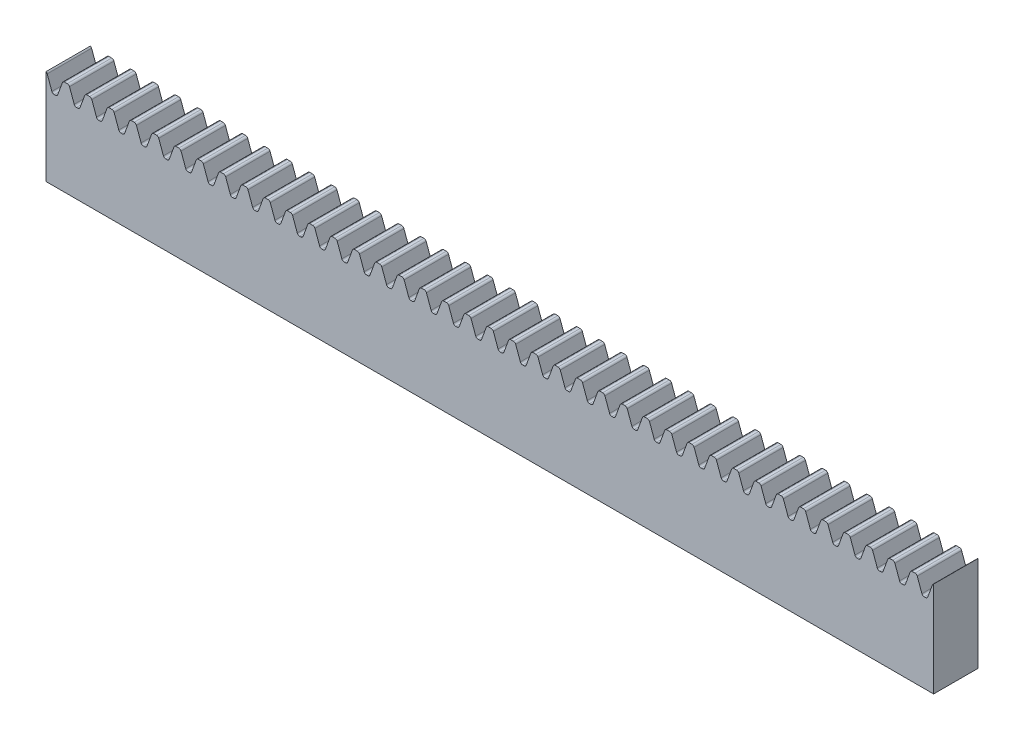
SolidWorks part; units mm, degrees
ref_plane "Front Plane" through (0, 0, 0) normal (0, 0, 1) x (1, 0, 0)
ref_plane "Top Plane" through (0, 0, 0) normal (0, 1, 0) x (1, 0, 0)
ref_plane "Right Plane" through (0, 0, 0) normal (1, 0, 0) x (0, 0, -1)
sketch "Sketch1" plane through (0, 0, 0) normal (0, 0, 1) x (1, 0, 0)
  line L0 (-50, 6.15) -> (-50, -6.15) construction
  line L1 (-50, -6.15) -> (50, -6.15) construction
  line L2 (50, -6.15) -> (50, 6.15) construction
  line L4 (0, 6.15) -> (0, -6.15) construction
  line L5 (-50, 5.35) -> (50, 5.35) construction
  line L6 (-48.0894, 6.15) -> (-47.4151, 6.15) construction
  line L7 (-47.4151, 6.15) -> (-46.7599, 4.35) construction
  line L8 (-48.0894, 6.15) -> (-48.7445, 4.35) construction
  line L9 (-48.7445, 4.35) -> (-46.7599, 4.35) construction
  line L10 (-47.7522, 6.15) -> (-47.7522, 4.35) construction
  line L11 (-50, 0) -> (-42.7257, 0) construction
  line L12 (50, 0) -> (42.7257, 0) construction
  point P15 (-45.2389, 6.15)
  point P16 (-19.5, -6.15)
  point P17 (-47.1239, 5.35)
  point P18 (-48.3805, 5.35)
  point P21 (-0.4, -6.15)
  dimension "Length" = 100
  dimension "Height" = 12.3
  dimension "Approximate Number of Teeth" = 39
  dimension "Pressure Angle" = 20
  dimension "Circular Pitch" = 2.5133
  dimension "Addendum" = 0.8
  dimension "Dedendum" = 1
  dimension "Circular Tooth Thickness" = 1.2566
  dimension "Module" = 0.8
  dimension "Rack Length" = 95.5044
  dimension "D1" = 5.0265
sketch "Sketch2" plane through (0, 0, 0) normal (1, 0, 0) x (0, 0, -1)
  line L0 (-4, 0) -> (4, 0) construction
  dimension "Face Width" = 8
sketch "Sketch3" plane through (0, 0, 0) normal (0, 0, 1) x (1, 0, 0)
  line L1 (-50, 6.15) -> (50, 6.15)
  line L2 (-50, 6.15) -> (-50, -6.15)
  line L3 (-50, -6.15) -> (50, -6.15)
  line L4 (50, 6.15) -> (50, -6.15)
extrude "Boss-Extrude1" add sketch "Sketch3" against normal up to vertex (4 mm away) and the other way up to vertex (4 mm away) up to point (0, 0, -4) other way up to point (0, 0, 4)
sketch "Sketch4" plane through (0, 0, 0) normal (0, 0, 1) x (1, 0, 0)
  line L0 (-47.7522, 6.15) -> (-45.2389, 6.15) construction
  line L9 (-46.4956, 6.15) -> (-46.4956, 4.35)
  line L10 (-46.4956, 4.35) -> (-46.7599, 4.35)
  line L11 (-46.7599, 4.35) -> (-47.4151, 6.15)
  line L12 (-47.4151, 6.15) -> (-46.4956, 6.15)
  line L13 (-48.0894, 6.15) -> (-48.7445, 4.35)
  line L14 (-48.7445, 4.35) -> (-49.0088, 4.35)
  line L15 (-49.0088, 4.35) -> (-49.0088, 6.15)
  line L16 (-49.0088, 6.15) -> (-48.0894, 6.15)
  line L17 (50, 6.15) -> (-50, 6.15) construction
  line L18 (-48.0894, 6.15) -> (-47.9014, 6.15)
  line L19 (-47.603, 6.15) -> (-47.4151, 6.15)
  arc A0 (-48.9324, 4.35) -> (-48.6802, 4.5266) centre (-48.9324, 4.6184) ccw
  arc A1 (-46.8242, 4.5266) -> (-46.572, 4.35) centre (-46.572, 4.6184) ccw
  arc A2 (-48.1536, 5.9734) -> (-47.9014, 6.15) centre (-47.9014, 5.8816) cw
  arc A3 (-47.603, 6.15) -> (-47.3508, 5.9734) centre (-47.603, 5.8816) cw
  dimension "D1" = 0.2684
extrude "Cut-Extrude1" cut sketch "Sketch4" against normal through all both and the other way through all contours L14 A0 L13 L16 L15 | L13 A2 L18 | L19 A3 L11 | L11 A1 L10 L9 L12 region at (-46.8223, 5.4223, 0) region at (-47.4415, 6.1123, 0) region at (-48.0629, 6.1123, 0) region at (-48.6821, 5.4223, 0)
pattern_linear "LPattern1" count 40 spacing 2.5133 along (1, 0, 0) count 2 spacing 2.5133 along (-1, 0, 0) of "Cut-Extrude1"
sketch "Drawing Refernce 1" plane through (0, 0, 4) normal (0, 0, 1) x (1, 0, 0)
  line L0 (-50, 0) -> (50, 0) construction
  point P6 (-35, 0)
  point P7 (-27.5, 0)
  point P8 (35, 0)
  dimension "D1" = 15
  dimension "D2" = 22.5
  dimension "D3" = 15
sketch "Sketch5" plane through (0, -6.15, 0) normal (0, -1, 0) x (1, 0, 0)
  line L1 (-50, 4) -> (50, 4)
  line L2 (-50, 4) -> (-50, -4)
  line L3 (-50, -4) -> (50, -4)
  line L4 (50, 4) -> (50, -4)
extrude "Cut-Extrude2" cut sketch "Sketch5" against normal blind 1.55
sketch "Sketch6" plane through (0, 0, -4) normal (0, 0, -1) x (-1, 0, 0)
  line L162 (-50, -4.6) -> (50, -4.6)
  line L163 (50, -4.6) -> (50, 6.1235)
  line L164 (49.8641, 5.9734) -> (49.3375, 4.5266)
  line L165 (49.0853, 4.35) -> (48.9324, 4.35)
  line L166 (48.6802, 4.5266) -> (48.1536, 5.9734)
  line L167 (47.9014, 6.15) -> (47.603, 6.15)
  line L168 (47.3508, 5.9734) -> (46.8242, 4.5266)
  line L169 (46.572, 4.35) -> (46.4192, 4.35)
  line L170 (46.1669, 4.5266) -> (45.6404, 5.9734)
  line L171 (45.3881, 6.15) -> (45.0897, 6.15)
  line L172 (44.8375, 5.9734) -> (44.3109, 4.5266)
  line L173 (44.0587, 4.35) -> (43.9059, 4.35)
  line L174 (43.6537, 4.5266) -> (43.1271, 5.9734)
  line L175 (42.8749, 6.15) -> (42.5765, 6.15)
  line L176 (42.3242, 5.9734) -> (41.7977, 4.5266)
  line L177 (41.5454, 4.35) -> (41.3926, 4.35)
  line L178 (41.1404, 4.5266) -> (40.6138, 5.9734)
  line L179 (40.3616, 6.15) -> (40.0632, 6.15)
  line L180 (39.811, 5.9734) -> (39.2844, 4.5266)
  line L181 (39.0322, 4.35) -> (38.8793, 4.35)
  line L182 (38.6271, 4.5266) -> (38.1005, 5.9734)
  line L183 (37.8483, 6.15) -> (37.5499, 6.15)
  line L184 (37.2977, 5.9734) -> (36.7711, 4.5266)
  line L185 (36.5189, 4.35) -> (36.3661, 4.35)
  line L186 (36.1138, 4.5266) -> (35.5873, 5.9734)
  line L187 (35.335, 6.15) -> (35.0366, 6.15)
  line L188 (34.7844, 5.9734) -> (34.2578, 4.5266)
  line L189 (34.0056, 4.35) -> (33.8528, 4.35)
  line L190 (33.6006, 4.5266) -> (33.074, 5.9734)
  line L191 (32.8218, 6.15) -> (32.5234, 6.15)
  line L192 (32.2711, 5.9734) -> (31.7446, 4.5266)
  line L193 (31.4923, 4.35) -> (31.3395, 4.35)
  line L194 (31.0873, 4.5266) -> (30.5607, 5.9734)
  line L195 (30.3085, 6.15) -> (30.0101, 6.15)
  line L196 (29.7579, 5.9734) -> (29.2313, 4.5266)
  line L197 (28.9791, 4.35) -> (28.8262, 4.35)
  line L198 (28.574, 4.5266) -> (28.0474, 5.9734)
  line L199 (27.7952, 6.15) -> (27.4968, 6.15)
  line L200 (27.2446, 5.9734) -> (26.718, 4.5266)
  line L201 (26.4658, 4.35) -> (26.313, 4.35)
  line L202 (26.0608, 4.5266) -> (25.5342, 5.9734)
  line L203 (25.2819, 6.15) -> (24.9835, 6.15)
  line L204 (24.7313, 5.9734) -> (24.2047, 4.5266)
  line L205 (23.9525, 4.35) -> (23.7997, 4.35)
  line L206 (23.5475, 4.5266) -> (23.0209, 5.9734)
  line L207 (22.7687, 6.15) -> (22.4703, 6.15)
  line L208 (22.218, 5.9734) -> (21.6915, 4.5266)
  line L209 (21.4392, 4.35) -> (21.2864, 4.35)
  line L210 (21.0342, 4.5266) -> (20.5076, 5.9734)
  line L211 (20.2554, 6.15) -> (19.957, 6.15)
  line L212 (19.7048, 5.9734) -> (19.1782, 4.5266)
  line L213 (18.926, 4.35) -> (18.7731, 4.35)
  line L214 (18.5209, 4.5266) -> (17.9943, 5.9734)
  line L215 (17.7421, 6.15) -> (17.4437, 6.15)
  line L216 (17.1915, 5.9734) -> (16.6649, 4.5266)
  line L217 (16.4127, 4.35) -> (16.2599, 4.35)
  line L218 (16.0077, 4.5266) -> (15.4811, 5.9734)
  line L219 (15.2288, 6.15) -> (14.9304, 6.15)
  line L220 (14.6782, 5.9734) -> (14.1516, 4.5266)
  line L221 (13.8994, 4.35) -> (13.7466, 4.35)
  line L222 (13.4944, 4.5266) -> (12.9678, 5.9734)
  line L223 (12.7156, 6.15) -> (12.4172, 6.15)
  line L224 (12.1649, 5.9734) -> (11.6384, 4.5266)
  line L225 (11.3861, 4.35) -> (11.2333, 4.35)
  line L226 (10.9811, 4.5266) -> (10.4545, 5.9734)
  line L227 (10.2023, 6.15) -> (9.9039, 6.15)
  line L228 (9.6517, 5.9734) -> (9.1251, 4.5266)
  line L229 (8.8729, 4.35) -> (8.72, 4.35)
  line L230 (8.4678, 4.5266) -> (7.9412, 5.9734)
  line L231 (7.689, 6.15) -> (7.3906, 6.15)
  line L232 (7.1384, 5.9734) -> (6.6118, 4.5266)
  line L233 (6.3596, 4.35) -> (6.2068, 4.35)
  line L234 (5.9546, 4.5266) -> (5.428, 5.9734)
  line L235 (5.1758, 6.15) -> (4.8773, 6.15)
  line L236 (4.6251, 5.9734) -> (4.0985, 4.5266)
  line L237 (3.8463, 4.35) -> (3.6935, 4.35)
  line L238 (3.4413, 4.5266) -> (2.9147, 5.9734)
  line L239 (2.6625, 6.15) -> (2.3641, 6.15)
  line L240 (2.1119, 5.9734) -> (1.5853, 4.5266)
  line L241 (1.333, 4.35) -> (1.1802, 4.35)
  line L242 (0.928, 4.5266) -> (0.4014, 5.9734)
  line L243 (0.1492, 6.15) -> (-0.1492, 6.15)
  line L244 (-0.4014, 5.9734) -> (-0.928, 4.5266)
  line L245 (-1.1802, 4.35) -> (-1.333, 4.35)
  line L246 (-1.5853, 4.5266) -> (-2.1119, 5.9734)
  line L247 (-2.3641, 6.15) -> (-2.6625, 6.15)
  line L248 (-2.9147, 5.9734) -> (-3.4413, 4.5266)
  line L249 (-3.6935, 4.35) -> (-3.8463, 4.35)
  line L250 (-4.0985, 4.5266) -> (-4.6251, 5.9734)
  line L251 (-4.8773, 6.15) -> (-5.1758, 6.15)
  line L252 (-5.428, 5.9734) -> (-5.9546, 4.5266)
  line L253 (-6.2068, 4.35) -> (-6.3596, 4.35)
  line L254 (-6.6118, 4.5266) -> (-7.1384, 5.9734)
  line L255 (-7.3906, 6.15) -> (-7.689, 6.15)
  line L256 (-7.9412, 5.9734) -> (-8.4678, 4.5266)
  line L257 (-8.72, 4.35) -> (-8.8729, 4.35)
  line L258 (-9.1251, 4.5266) -> (-9.6517, 5.9734)
  line L259 (-9.9039, 6.15) -> (-10.2023, 6.15)
  line L260 (-10.4545, 5.9734) -> (-10.9811, 4.5266)
  line L261 (-11.2333, 4.35) -> (-11.3861, 4.35)
  line L262 (-11.6384, 4.5266) -> (-12.1649, 5.9734)
  line L263 (-12.4172, 6.15) -> (-12.7156, 6.15)
  line L264 (-12.9678, 5.9734) -> (-13.4944, 4.5266)
  line L265 (-13.7466, 4.35) -> (-13.8994, 4.35)
  line L266 (-14.1516, 4.5266) -> (-14.6782, 5.9734)
  line L267 (-14.9304, 6.15) -> (-15.2288, 6.15)
  line L268 (-15.4811, 5.9734) -> (-16.0077, 4.5266)
  line L269 (-16.2599, 4.35) -> (-16.4127, 4.35)
  line L270 (-16.6649, 4.5266) -> (-17.1915, 5.9734)
  line L271 (-17.4437, 6.15) -> (-17.7421, 6.15)
  line L272 (-17.9943, 5.9734) -> (-18.5209, 4.5266)
  line L273 (-18.7731, 4.35) -> (-18.926, 4.35)
  line L274 (-19.1782, 4.5266) -> (-19.7048, 5.9734)
  line L275 (-19.957, 6.15) -> (-20.2554, 6.15)
  line L276 (-20.5076, 5.9734) -> (-21.0342, 4.5266)
  line L277 (-21.2864, 4.35) -> (-21.4392, 4.35)
  line L278 (-21.6915, 4.5266) -> (-22.218, 5.9734)
  line L279 (-22.4703, 6.15) -> (-22.7687, 6.15)
  line L280 (-23.0209, 5.9734) -> (-23.5475, 4.5266)
  line L281 (-23.7997, 4.35) -> (-23.9525, 4.35)
  line L282 (-24.2047, 4.5266) -> (-24.7313, 5.9734)
  line L283 (-24.9835, 6.15) -> (-25.2819, 6.15)
  line L284 (-25.5342, 5.9734) -> (-26.0608, 4.5266)
  line L285 (-26.313, 4.35) -> (-26.4658, 4.35)
  line L286 (-26.718, 4.5266) -> (-27.2446, 5.9734)
  line L287 (-27.4968, 6.15) -> (-27.7952, 6.15)
  line L288 (-28.0474, 5.9734) -> (-28.574, 4.5266)
  line L289 (-28.8262, 4.35) -> (-28.9791, 4.35)
  line L290 (-29.2313, 4.5266) -> (-29.7579, 5.9734)
  line L291 (-30.0101, 6.15) -> (-30.3085, 6.15)
  line L292 (-30.5607, 5.9734) -> (-31.0873, 4.5266)
  line L293 (-31.3395, 4.35) -> (-31.4923, 4.35)
  line L294 (-31.7446, 4.5266) -> (-32.2711, 5.9734)
  line L295 (-32.5234, 6.15) -> (-32.8218, 6.15)
  line L296 (-33.074, 5.9734) -> (-33.6006, 4.5266)
  line L297 (-33.8528, 4.35) -> (-34.0056, 4.35)
  line L298 (-34.2578, 4.5266) -> (-34.7844, 5.9734)
  line L299 (-35.0366, 6.15) -> (-35.335, 6.15)
  line L300 (-35.5873, 5.9734) -> (-36.1138, 4.5266)
  line L301 (-36.3661, 4.35) -> (-36.5189, 4.35)
  line L302 (-36.7711, 4.5266) -> (-37.2977, 5.9734)
  line L303 (-37.5499, 6.15) -> (-37.8483, 6.15)
  line L304 (-38.1005, 5.9734) -> (-38.6271, 4.5266)
  line L305 (-38.8793, 4.35) -> (-39.0322, 4.35)
  line L306 (-39.2844, 4.5266) -> (-39.811, 5.9734)
  line L307 (-40.0632, 6.15) -> (-40.3616, 6.15)
  line L308 (-40.6138, 5.9734) -> (-41.1404, 4.5266)
  line L309 (-41.3926, 4.35) -> (-41.5454, 4.35)
  line L310 (-41.7977, 4.5266) -> (-42.3242, 5.9734)
  line L311 (-42.5765, 6.15) -> (-42.8749, 6.15)
  line L312 (-43.1271, 5.9734) -> (-43.6537, 4.5266)
  line L313 (-43.9059, 4.35) -> (-44.0587, 4.35)
  line L314 (-44.3109, 4.5266) -> (-44.8375, 5.9734)
  line L315 (-45.0897, 6.15) -> (-45.3881, 6.15)
  line L316 (-45.6404, 5.9734) -> (-46.1669, 4.5266)
  line L317 (-46.4192, 4.35) -> (-46.572, 4.35)
  line L318 (-46.8242, 4.5266) -> (-47.3508, 5.9734)
  line L319 (-47.603, 6.15) -> (-47.9014, 6.15)
  line L320 (-48.1536, 5.9734) -> (-48.6802, 4.5266)
  line L321 (-48.9324, 4.35) -> (-49.0853, 4.35)
  line L322 (-49.3375, 4.5266) -> (-49.8641, 5.9734)
  line L323 (-50, 6.1235) -> (-50, -4.6)
  line L325 (50, -4.6) -> (50, 6.1235)
  line L326 (49.8641, 5.9734) -> (49.3375, 4.5266)
  line L327 (49.0853, 4.35) -> (48.9324, 4.35)
  line L328 (48.6802, 4.5266) -> (48.1536, 5.9734)
  line L329 (47.9014, 6.15) -> (47.603, 6.15)
  line L330 (47.3508, 5.9734) -> (46.8242, 4.5266)
  line L331 (46.572, 4.35) -> (46.4192, 4.35)
  line L332 (46.1669, 4.5266) -> (45.6404, 5.9734)
  line L333 (45.3881, 6.15) -> (45.0897, 6.15)
  line L334 (44.8375, 5.9734) -> (44.3109, 4.5266)
  line L335 (44.0587, 4.35) -> (43.9059, 4.35)
  line L336 (43.6537, 4.5266) -> (43.1271, 5.9734)
  line L337 (42.8749, 6.15) -> (42.5765, 6.15)
  line L338 (42.3242, 5.9734) -> (41.7977, 4.5266)
  line L339 (41.5454, 4.35) -> (41.3926, 4.35)
  line L340 (41.1404, 4.5266) -> (40.6138, 5.9734)
  line L341 (40.3616, 6.15) -> (40.0632, 6.15)
  line L342 (39.811, 5.9734) -> (39.2844, 4.5266)
  line L343 (39.0322, 4.35) -> (38.8793, 4.35)
  line L344 (38.6271, 4.5266) -> (38.1005, 5.9734)
  line L345 (37.8483, 6.15) -> (37.5499, 6.15)
  line L346 (37.2977, 5.9734) -> (36.7711, 4.5266)
  line L347 (36.5189, 4.35) -> (36.3661, 4.35)
  line L348 (36.1138, 4.5266) -> (35.5873, 5.9734)
  line L349 (35.335, 6.15) -> (35.0366, 6.15)
  line L350 (34.7844, 5.9734) -> (34.2578, 4.5266)
  line L351 (34.0056, 4.35) -> (33.8528, 4.35)
  line L352 (33.6006, 4.5266) -> (33.074, 5.9734)
  line L353 (32.8218, 6.15) -> (32.5234, 6.15)
  line L354 (32.2711, 5.9734) -> (31.7446, 4.5266)
  line L355 (31.4923, 4.35) -> (31.3395, 4.35)
  line L356 (31.0873, 4.5266) -> (30.5607, 5.9734)
  line L357 (30.3085, 6.15) -> (30.0101, 6.15)
  line L358 (29.7579, 5.9734) -> (29.2313, 4.5266)
  line L359 (28.9791, 4.35) -> (28.8262, 4.35)
  line L360 (28.574, 4.5266) -> (28.0474, 5.9734)
  line L361 (27.7952, 6.15) -> (27.4968, 6.15)
  line L362 (27.2446, 5.9734) -> (26.718, 4.5266)
  line L363 (26.4658, 4.35) -> (26.313, 4.35)
  line L364 (26.0608, 4.5266) -> (25.5342, 5.9734)
  line L365 (25.2819, 6.15) -> (24.9835, 6.15)
  line L366 (24.7313, 5.9734) -> (24.2047, 4.5266)
  line L367 (23.9525, 4.35) -> (23.7997, 4.35)
  line L368 (23.5475, 4.5266) -> (23.0209, 5.9734)
  line L369 (22.7687, 6.15) -> (22.4703, 6.15)
  line L370 (22.218, 5.9734) -> (21.6915, 4.5266)
  line L371 (21.4392, 4.35) -> (21.2864, 4.35)
  line L372 (21.0342, 4.5266) -> (20.5076, 5.9734)
  line L373 (20.2554, 6.15) -> (19.957, 6.15)
  line L374 (19.7048, 5.9734) -> (19.1782, 4.5266)
  line L375 (18.926, 4.35) -> (18.7731, 4.35)
  line L376 (18.5209, 4.5266) -> (17.9943, 5.9734)
  line L377 (17.7421, 6.15) -> (17.4437, 6.15)
  line L378 (17.1915, 5.9734) -> (16.6649, 4.5266)
  line L379 (16.4127, 4.35) -> (16.2599, 4.35)
  line L380 (16.0077, 4.5266) -> (15.4811, 5.9734)
  line L381 (15.2288, 6.15) -> (14.9304, 6.15)
  line L382 (14.6782, 5.9734) -> (14.1516, 4.5266)
  line L383 (13.8994, 4.35) -> (13.7466, 4.35)
  line L384 (13.4944, 4.5266) -> (12.9678, 5.9734)
  line L385 (12.7156, 6.15) -> (12.4172, 6.15)
  line L386 (12.1649, 5.9734) -> (11.6384, 4.5266)
  line L387 (11.3861, 4.35) -> (11.2333, 4.35)
  line L388 (10.9811, 4.5266) -> (10.4545, 5.9734)
  line L389 (10.2023, 6.15) -> (9.9039, 6.15)
  line L390 (9.6517, 5.9734) -> (9.1251, 4.5266)
  line L391 (8.8729, 4.35) -> (8.72, 4.35)
  line L392 (8.4678, 4.5266) -> (7.9412, 5.9734)
  line L393 (7.689, 6.15) -> (7.3906, 6.15)
  line L394 (7.1384, 5.9734) -> (6.6118, 4.5266)
  line L395 (6.3596, 4.35) -> (6.2068, 4.35)
  line L396 (5.9546, 4.5266) -> (5.428, 5.9734)
  line L397 (5.1758, 6.15) -> (4.8773, 6.15)
  line L398 (4.6251, 5.9734) -> (4.0985, 4.5266)
  line L399 (3.8463, 4.35) -> (3.6935, 4.35)
  line L400 (3.4413, 4.5266) -> (2.9147, 5.9734)
  line L401 (2.6625, 6.15) -> (2.3641, 6.15)
  line L402 (2.1119, 5.9734) -> (1.5853, 4.5266)
  line L403 (1.333, 4.35) -> (1.1802, 4.35)
  line L404 (0.928, 4.5266) -> (0.4014, 5.9734)
  line L405 (0.1492, 6.15) -> (-0.1492, 6.15)
  line L406 (-0.4014, 5.9734) -> (-0.928, 4.5266)
  line L407 (-1.1802, 4.35) -> (-1.333, 4.35)
  line L408 (-1.5853, 4.5266) -> (-2.1119, 5.9734)
  line L409 (-2.3641, 6.15) -> (-2.6625, 6.15)
  line L410 (-2.9147, 5.9734) -> (-3.4413, 4.5266)
  line L411 (-3.6935, 4.35) -> (-3.8463, 4.35)
  line L412 (-4.0985, 4.5266) -> (-4.6251, 5.9734)
  line L413 (-4.8773, 6.15) -> (-5.1758, 6.15)
  line L414 (-5.428, 5.9734) -> (-5.9546, 4.5266)
  line L415 (-6.2068, 4.35) -> (-6.3596, 4.35)
  line L416 (-6.6118, 4.5266) -> (-7.1384, 5.9734)
  line L417 (-7.3906, 6.15) -> (-7.689, 6.15)
  line L418 (-7.9412, 5.9734) -> (-8.4678, 4.5266)
  line L419 (-8.72, 4.35) -> (-8.8729, 4.35)
  line L420 (-9.1251, 4.5266) -> (-9.6517, 5.9734)
  line L421 (-9.9039, 6.15) -> (-10.2023, 6.15)
  line L422 (-10.4545, 5.9734) -> (-10.9811, 4.5266)
  line L423 (-11.2333, 4.35) -> (-11.3861, 4.35)
  line L424 (-11.6384, 4.5266) -> (-12.1649, 5.9734)
  line L425 (-12.4172, 6.15) -> (-12.7156, 6.15)
  line L426 (-12.9678, 5.9734) -> (-13.4944, 4.5266)
  line L427 (-13.7466, 4.35) -> (-13.8994, 4.35)
  line L428 (-14.1516, 4.5266) -> (-14.6782, 5.9734)
  line L429 (-14.9304, 6.15) -> (-15.2288, 6.15)
  line L430 (-15.4811, 5.9734) -> (-16.0077, 4.5266)
  line L431 (-16.2599, 4.35) -> (-16.4127, 4.35)
  line L432 (-16.6649, 4.5266) -> (-17.1915, 5.9734)
  line L433 (-17.4437, 6.15) -> (-17.7421, 6.15)
  line L434 (-17.9943, 5.9734) -> (-18.5209, 4.5266)
  line L435 (-18.7731, 4.35) -> (-18.926, 4.35)
  line L436 (-19.1782, 4.5266) -> (-19.7048, 5.9734)
  line L437 (-19.957, 6.15) -> (-20.2554, 6.15)
  line L438 (-20.5076, 5.9734) -> (-21.0342, 4.5266)
  line L439 (-21.2864, 4.35) -> (-21.4392, 4.35)
  line L440 (-21.6915, 4.5266) -> (-22.218, 5.9734)
  line L441 (-22.4703, 6.15) -> (-22.7687, 6.15)
  line L442 (-23.0209, 5.9734) -> (-23.5475, 4.5266)
  line L443 (-23.7997, 4.35) -> (-23.9525, 4.35)
  line L444 (-24.2047, 4.5266) -> (-24.7313, 5.9734)
  line L445 (-24.9835, 6.15) -> (-25.2819, 6.15)
  line L446 (-25.5342, 5.9734) -> (-26.0608, 4.5266)
  line L447 (-26.313, 4.35) -> (-26.4658, 4.35)
  line L448 (-26.718, 4.5266) -> (-27.2446, 5.9734)
  line L449 (-27.4968, 6.15) -> (-27.7952, 6.15)
  line L450 (-28.0474, 5.9734) -> (-28.574, 4.5266)
  line L451 (-28.8262, 4.35) -> (-28.9791, 4.35)
  line L452 (-29.2313, 4.5266) -> (-29.7579, 5.9734)
  line L453 (-30.0101, 6.15) -> (-30.3085, 6.15)
  line L454 (-30.5607, 5.9734) -> (-31.0873, 4.5266)
  line L455 (-31.3395, 4.35) -> (-31.4923, 4.35)
  line L456 (-31.7446, 4.5266) -> (-32.2711, 5.9734)
  line L457 (-32.5234, 6.15) -> (-32.8218, 6.15)
  line L458 (-33.074, 5.9734) -> (-33.6006, 4.5266)
  line L459 (-33.8528, 4.35) -> (-34.0056, 4.35)
  line L460 (-34.2578, 4.5266) -> (-34.7844, 5.9734)
  line L461 (-35.0366, 6.15) -> (-35.335, 6.15)
  line L462 (-35.5873, 5.9734) -> (-36.1138, 4.5266)
  line L463 (-36.3661, 4.35) -> (-36.5189, 4.35)
  line L464 (-36.7711, 4.5266) -> (-37.2977, 5.9734)
  line L465 (-37.5499, 6.15) -> (-37.8483, 6.15)
  line L466 (-38.1005, 5.9734) -> (-38.6271, 4.5266)
  line L467 (-38.8793, 4.35) -> (-39.0322, 4.35)
  line L468 (-39.2844, 4.5266) -> (-39.811, 5.9734)
  line L469 (-40.0632, 6.15) -> (-40.3616, 6.15)
  line L470 (-40.6138, 5.9734) -> (-41.1404, 4.5266)
  line L471 (-41.3926, 4.35) -> (-41.5454, 4.35)
  line L472 (-41.7977, 4.5266) -> (-42.3242, 5.9734)
  line L473 (-42.5765, 6.15) -> (-42.8749, 6.15)
  line L474 (-43.1271, 5.9734) -> (-43.6537, 4.5266)
  line L475 (-43.9059, 4.35) -> (-44.0587, 4.35)
  line L476 (-44.3109, 4.5266) -> (-44.8375, 5.9734)
  line L477 (-45.0897, 6.15) -> (-45.3881, 6.15)
  line L478 (-45.6404, 5.9734) -> (-46.1669, 4.5266)
  line L479 (-46.4192, 4.35) -> (-46.572, 4.35)
  line L480 (-46.8242, 4.5266) -> (-47.3508, 5.9734)
  line L481 (-47.603, 6.15) -> (-47.9014, 6.15)
  line L482 (-48.1536, 5.9734) -> (-48.6802, 4.5266)
  line L483 (-48.9324, 4.35) -> (-49.0853, 4.35)
  line L484 (-49.3375, 4.5266) -> (-49.8641, 5.9734)
  line L485 (-50, 6.1235) -> (-50, -4.6)
  line L487 (-50, -4.6) -> (50, -4.6)
  arc A160 (50, 6.1235) -> (49.8641, 5.9734) centre (50.1163, 5.8816) ccw
  arc A161 (49.0853, 4.35) -> (49.3375, 4.5266) centre (49.0853, 4.6184) ccw
  arc A162 (48.6802, 4.5266) -> (48.9324, 4.35) centre (48.9324, 4.6184) ccw
  arc A163 (48.1536, 5.9734) -> (47.9014, 6.15) centre (47.9014, 5.8816) ccw
  arc A164 (47.603, 6.15) -> (47.3508, 5.9734) centre (47.603, 5.8816) ccw
  arc A165 (46.572, 4.35) -> (46.8242, 4.5266) centre (46.572, 4.6184) ccw
  arc A166 (46.1669, 4.5266) -> (46.4192, 4.35) centre (46.4192, 4.6184) ccw
  arc A167 (45.6404, 5.9734) -> (45.3881, 6.15) centre (45.3881, 5.8816) ccw
  arc A168 (45.0897, 6.15) -> (44.8375, 5.9734) centre (45.0897, 5.8816) ccw
  arc A169 (44.0587, 4.35) -> (44.3109, 4.5266) centre (44.0587, 4.6184) ccw
  arc A170 (43.6537, 4.5266) -> (43.9059, 4.35) centre (43.9059, 4.6184) ccw
  arc A171 (43.1271, 5.9734) -> (42.8749, 6.15) centre (42.8749, 5.8816) ccw
  arc A172 (42.5765, 6.15) -> (42.3242, 5.9734) centre (42.5765, 5.8816) ccw
  arc A173 (41.5454, 4.35) -> (41.7977, 4.5266) centre (41.5454, 4.6184) ccw
  arc A174 (41.1404, 4.5266) -> (41.3926, 4.35) centre (41.3926, 4.6184) ccw
  arc A175 (40.6138, 5.9734) -> (40.3616, 6.15) centre (40.3616, 5.8816) ccw
  arc A176 (40.0632, 6.15) -> (39.811, 5.9734) centre (40.0632, 5.8816) ccw
  arc A177 (39.0322, 4.35) -> (39.2844, 4.5266) centre (39.0322, 4.6184) ccw
  arc A178 (38.6271, 4.5266) -> (38.8793, 4.35) centre (38.8793, 4.6184) ccw
  arc A179 (38.1005, 5.9734) -> (37.8483, 6.15) centre (37.8483, 5.8816) ccw
  arc A180 (37.5499, 6.15) -> (37.2977, 5.9734) centre (37.5499, 5.8816) ccw
  arc A181 (36.5189, 4.35) -> (36.7711, 4.5266) centre (36.5189, 4.6184) ccw
  arc A182 (36.1138, 4.5266) -> (36.3661, 4.35) centre (36.3661, 4.6184) ccw
  arc A183 (35.5873, 5.9734) -> (35.335, 6.15) centre (35.335, 5.8816) ccw
  arc A184 (35.0366, 6.15) -> (34.7844, 5.9734) centre (35.0366, 5.8816) ccw
  arc A185 (34.0056, 4.35) -> (34.2578, 4.5266) centre (34.0056, 4.6184) ccw
  arc A186 (33.6006, 4.5266) -> (33.8528, 4.35) centre (33.8528, 4.6184) ccw
  arc A187 (33.074, 5.9734) -> (32.8218, 6.15) centre (32.8218, 5.8816) ccw
  arc A188 (32.5234, 6.15) -> (32.2711, 5.9734) centre (32.5234, 5.8816) ccw
  arc A189 (31.4923, 4.35) -> (31.7446, 4.5266) centre (31.4923, 4.6184) ccw
  arc A190 (31.0873, 4.5266) -> (31.3395, 4.35) centre (31.3395, 4.6184) ccw
  arc A191 (30.5607, 5.9734) -> (30.3085, 6.15) centre (30.3085, 5.8816) ccw
  arc A192 (30.0101, 6.15) -> (29.7579, 5.9734) centre (30.0101, 5.8816) ccw
  arc A193 (28.9791, 4.35) -> (29.2313, 4.5266) centre (28.9791, 4.6184) ccw
  arc A194 (28.574, 4.5266) -> (28.8262, 4.35) centre (28.8262, 4.6184) ccw
  arc A195 (28.0474, 5.9734) -> (27.7952, 6.15) centre (27.7952, 5.8816) ccw
  arc A196 (27.4968, 6.15) -> (27.2446, 5.9734) centre (27.4968, 5.8816) ccw
  arc A197 (26.4658, 4.35) -> (26.718, 4.5266) centre (26.4658, 4.6184) ccw
  arc A198 (26.0608, 4.5266) -> (26.313, 4.35) centre (26.313, 4.6184) ccw
  arc A199 (25.5342, 5.9734) -> (25.2819, 6.15) centre (25.2819, 5.8816) ccw
  arc A200 (24.9835, 6.15) -> (24.7313, 5.9734) centre (24.9835, 5.8816) ccw
  arc A201 (23.9525, 4.35) -> (24.2047, 4.5266) centre (23.9525, 4.6184) ccw
  arc A202 (23.5475, 4.5266) -> (23.7997, 4.35) centre (23.7997, 4.6184) ccw
  arc A203 (23.0209, 5.9734) -> (22.7687, 6.15) centre (22.7687, 5.8816) ccw
  arc A204 (22.4703, 6.15) -> (22.218, 5.9734) centre (22.4703, 5.8816) ccw
  arc A205 (21.4392, 4.35) -> (21.6915, 4.5266) centre (21.4392, 4.6184) ccw
  arc A206 (21.0342, 4.5266) -> (21.2864, 4.35) centre (21.2864, 4.6184) ccw
  arc A207 (20.5076, 5.9734) -> (20.2554, 6.15) centre (20.2554, 5.8816) ccw
  arc A208 (19.957, 6.15) -> (19.7048, 5.9734) centre (19.957, 5.8816) ccw
  arc A209 (18.926, 4.35) -> (19.1782, 4.5266) centre (18.926, 4.6184) ccw
  arc A210 (18.5209, 4.5266) -> (18.7731, 4.35) centre (18.7731, 4.6184) ccw
  arc A211 (17.9943, 5.9734) -> (17.7421, 6.15) centre (17.7421, 5.8816) ccw
  arc A212 (17.4437, 6.15) -> (17.1915, 5.9734) centre (17.4437, 5.8816) ccw
  arc A213 (16.4127, 4.35) -> (16.6649, 4.5266) centre (16.4127, 4.6184) ccw
  arc A214 (16.0077, 4.5266) -> (16.2599, 4.35) centre (16.2599, 4.6184) ccw
  arc A215 (15.4811, 5.9734) -> (15.2288, 6.15) centre (15.2288, 5.8816) ccw
  arc A216 (14.9304, 6.15) -> (14.6782, 5.9734) centre (14.9304, 5.8816) ccw
  arc A217 (13.8994, 4.35) -> (14.1516, 4.5266) centre (13.8994, 4.6184) ccw
  arc A218 (13.4944, 4.5266) -> (13.7466, 4.35) centre (13.7466, 4.6184) ccw
  arc A219 (12.9678, 5.9734) -> (12.7156, 6.15) centre (12.7156, 5.8816) ccw
  arc A220 (12.4172, 6.15) -> (12.1649, 5.9734) centre (12.4172, 5.8816) ccw
  arc A221 (11.3861, 4.35) -> (11.6384, 4.5266) centre (11.3861, 4.6184) ccw
  arc A222 (10.9811, 4.5266) -> (11.2333, 4.35) centre (11.2333, 4.6184) ccw
  arc A223 (10.4545, 5.9734) -> (10.2023, 6.15) centre (10.2023, 5.8816) ccw
  arc A224 (9.9039, 6.15) -> (9.6517, 5.9734) centre (9.9039, 5.8816) ccw
  arc A225 (8.8729, 4.35) -> (9.1251, 4.5266) centre (8.8729, 4.6184) ccw
  arc A226 (8.4678, 4.5266) -> (8.72, 4.35) centre (8.72, 4.6184) ccw
  arc A227 (7.9412, 5.9734) -> (7.689, 6.15) centre (7.689, 5.8816) ccw
  arc A228 (7.3906, 6.15) -> (7.1384, 5.9734) centre (7.3906, 5.8816) ccw
  arc A229 (6.3596, 4.35) -> (6.6118, 4.5266) centre (6.3596, 4.6184) ccw
  arc A230 (5.9546, 4.5266) -> (6.2068, 4.35) centre (6.2068, 4.6184) ccw
  arc A231 (5.428, 5.9734) -> (5.1758, 6.15) centre (5.1758, 5.8816) ccw
  arc A232 (4.8773, 6.15) -> (4.6251, 5.9734) centre (4.8773, 5.8816) ccw
  arc A233 (3.8463, 4.35) -> (4.0985, 4.5266) centre (3.8463, 4.6184) ccw
  arc A234 (3.4413, 4.5266) -> (3.6935, 4.35) centre (3.6935, 4.6184) ccw
  arc A235 (2.9147, 5.9734) -> (2.6625, 6.15) centre (2.6625, 5.8816) ccw
  arc A236 (2.3641, 6.15) -> (2.1119, 5.9734) centre (2.3641, 5.8816) ccw
  arc A237 (1.333, 4.35) -> (1.5853, 4.5266) centre (1.333, 4.6184) ccw
  arc A238 (0.928, 4.5266) -> (1.1802, 4.35) centre (1.1802, 4.6184) ccw
  arc A239 (0.4014, 5.9734) -> (0.1492, 6.15) centre (0.1492, 5.8816) ccw
  arc A240 (-0.1492, 6.15) -> (-0.4014, 5.9734) centre (-0.1492, 5.8816) ccw
  arc A241 (-1.1802, 4.35) -> (-0.928, 4.5266) centre (-1.1802, 4.6184) ccw
  arc A242 (-1.5853, 4.5266) -> (-1.333, 4.35) centre (-1.333, 4.6184) ccw
  arc A243 (-2.1119, 5.9734) -> (-2.3641, 6.15) centre (-2.3641, 5.8816) ccw
  arc A244 (-2.6625, 6.15) -> (-2.9147, 5.9734) centre (-2.6625, 5.8816) ccw
  arc A245 (-3.6935, 4.35) -> (-3.4413, 4.5266) centre (-3.6935, 4.6184) ccw
  arc A246 (-4.0985, 4.5266) -> (-3.8463, 4.35) centre (-3.8463, 4.6184) ccw
  arc A247 (-4.6251, 5.9734) -> (-4.8773, 6.15) centre (-4.8773, 5.8816) ccw
  arc A248 (-5.1758, 6.15) -> (-5.428, 5.9734) centre (-5.1758, 5.8816) ccw
  arc A249 (-6.2068, 4.35) -> (-5.9546, 4.5266) centre (-6.2068, 4.6184) ccw
  arc A250 (-6.6118, 4.5266) -> (-6.3596, 4.35) centre (-6.3596, 4.6184) ccw
  arc A251 (-7.1384, 5.9734) -> (-7.3906, 6.15) centre (-7.3906, 5.8816) ccw
  arc A252 (-7.689, 6.15) -> (-7.9412, 5.9734) centre (-7.689, 5.8816) ccw
  arc A253 (-8.72, 4.35) -> (-8.4678, 4.5266) centre (-8.72, 4.6184) ccw
  arc A254 (-9.1251, 4.5266) -> (-8.8729, 4.35) centre (-8.8729, 4.6184) ccw
  arc A255 (-9.6517, 5.9734) -> (-9.9039, 6.15) centre (-9.9039, 5.8816) ccw
  arc A256 (-10.2023, 6.15) -> (-10.4545, 5.9734) centre (-10.2023, 5.8816) ccw
  arc A257 (-11.2333, 4.35) -> (-10.9811, 4.5266) centre (-11.2333, 4.6184) ccw
  arc A258 (-11.6384, 4.5266) -> (-11.3861, 4.35) centre (-11.3861, 4.6184) ccw
  arc A259 (-12.1649, 5.9734) -> (-12.4172, 6.15) centre (-12.4172, 5.8816) ccw
  arc A260 (-12.7156, 6.15) -> (-12.9678, 5.9734) centre (-12.7156, 5.8816) ccw
  arc A261 (-13.7466, 4.35) -> (-13.4944, 4.5266) centre (-13.7466, 4.6184) ccw
  arc A262 (-14.1516, 4.5266) -> (-13.8994, 4.35) centre (-13.8994, 4.6184) ccw
  arc A263 (-14.6782, 5.9734) -> (-14.9304, 6.15) centre (-14.9304, 5.8816) ccw
  arc A264 (-15.2288, 6.15) -> (-15.4811, 5.9734) centre (-15.2288, 5.8816) ccw
  arc A265 (-16.2599, 4.35) -> (-16.0077, 4.5266) centre (-16.2599, 4.6184) ccw
  arc A266 (-16.6649, 4.5266) -> (-16.4127, 4.35) centre (-16.4127, 4.6184) ccw
  arc A267 (-17.1915, 5.9734) -> (-17.4437, 6.15) centre (-17.4437, 5.8816) ccw
  arc A268 (-17.7421, 6.15) -> (-17.9943, 5.9734) centre (-17.7421, 5.8816) ccw
  arc A269 (-18.7731, 4.35) -> (-18.5209, 4.5266) centre (-18.7731, 4.6184) ccw
  arc A270 (-19.1782, 4.5266) -> (-18.926, 4.35) centre (-18.926, 4.6184) ccw
  arc A271 (-19.7048, 5.9734) -> (-19.957, 6.15) centre (-19.957, 5.8816) ccw
  arc A272 (-20.2554, 6.15) -> (-20.5076, 5.9734) centre (-20.2554, 5.8816) ccw
  arc A273 (-21.2864, 4.35) -> (-21.0342, 4.5266) centre (-21.2864, 4.6184) ccw
  arc A274 (-21.6915, 4.5266) -> (-21.4392, 4.35) centre (-21.4392, 4.6184) ccw
  arc A275 (-22.218, 5.9734) -> (-22.4703, 6.15) centre (-22.4703, 5.8816) ccw
  arc A276 (-22.7687, 6.15) -> (-23.0209, 5.9734) centre (-22.7687, 5.8816) ccw
  arc A277 (-23.7997, 4.35) -> (-23.5475, 4.5266) centre (-23.7997, 4.6184) ccw
  arc A278 (-24.2047, 4.5266) -> (-23.9525, 4.35) centre (-23.9525, 4.6184) ccw
  arc A279 (-24.7313, 5.9734) -> (-24.9835, 6.15) centre (-24.9835, 5.8816) ccw
  arc A280 (-25.2819, 6.15) -> (-25.5342, 5.9734) centre (-25.2819, 5.8816) ccw
  arc A281 (-26.313, 4.35) -> (-26.0608, 4.5266) centre (-26.313, 4.6184) ccw
  arc A282 (-26.718, 4.5266) -> (-26.4658, 4.35) centre (-26.4658, 4.6184) ccw
  arc A283 (-27.2446, 5.9734) -> (-27.4968, 6.15) centre (-27.4968, 5.8816) ccw
  arc A284 (-27.7952, 6.15) -> (-28.0474, 5.9734) centre (-27.7952, 5.8816) ccw
  arc A285 (-28.8262, 4.35) -> (-28.574, 4.5266) centre (-28.8262, 4.6184) ccw
  arc A286 (-29.2313, 4.5266) -> (-28.9791, 4.35) centre (-28.9791, 4.6184) ccw
  arc A287 (-29.7579, 5.9734) -> (-30.0101, 6.15) centre (-30.0101, 5.8816) ccw
  arc A288 (-30.3085, 6.15) -> (-30.5607, 5.9734) centre (-30.3085, 5.8816) ccw
  arc A289 (-31.3395, 4.35) -> (-31.0873, 4.5266) centre (-31.3395, 4.6184) ccw
  arc A290 (-31.7446, 4.5266) -> (-31.4923, 4.35) centre (-31.4923, 4.6184) ccw
  arc A291 (-32.2711, 5.9734) -> (-32.5234, 6.15) centre (-32.5234, 5.8816) ccw
  arc A292 (-32.8218, 6.15) -> (-33.074, 5.9734) centre (-32.8218, 5.8816) ccw
  arc A293 (-33.8528, 4.35) -> (-33.6006, 4.5266) centre (-33.8528, 4.6184) ccw
  arc A294 (-34.2578, 4.5266) -> (-34.0056, 4.35) centre (-34.0056, 4.6184) ccw
  arc A295 (-34.7844, 5.9734) -> (-35.0366, 6.15) centre (-35.0366, 5.8816) ccw
  arc A296 (-35.335, 6.15) -> (-35.5873, 5.9734) centre (-35.335, 5.8816) ccw
  arc A297 (-36.3661, 4.35) -> (-36.1138, 4.5266) centre (-36.3661, 4.6184) ccw
  arc A298 (-36.7711, 4.5266) -> (-36.5189, 4.35) centre (-36.5189, 4.6184) ccw
  arc A299 (-37.2977, 5.9734) -> (-37.5499, 6.15) centre (-37.5499, 5.8816) ccw
  arc A300 (-37.8483, 6.15) -> (-38.1005, 5.9734) centre (-37.8483, 5.8816) ccw
  arc A301 (-38.8793, 4.35) -> (-38.6271, 4.5266) centre (-38.8793, 4.6184) ccw
  arc A302 (-39.2844, 4.5266) -> (-39.0322, 4.35) centre (-39.0322, 4.6184) ccw
  arc A303 (-39.811, 5.9734) -> (-40.0632, 6.15) centre (-40.0632, 5.8816) ccw
  arc A304 (-40.3616, 6.15) -> (-40.6138, 5.9734) centre (-40.3616, 5.8816) ccw
  arc A305 (-41.3926, 4.35) -> (-41.1404, 4.5266) centre (-41.3926, 4.6184) ccw
  arc A306 (-41.7977, 4.5266) -> (-41.5454, 4.35) centre (-41.5454, 4.6184) ccw
  arc A307 (-42.3242, 5.9734) -> (-42.5765, 6.15) centre (-42.5765, 5.8816) ccw
  arc A308 (-42.8749, 6.15) -> (-43.1271, 5.9734) centre (-42.8749, 5.8816) ccw
  arc A309 (-43.9059, 4.35) -> (-43.6537, 4.5266) centre (-43.9059, 4.6184) ccw
  arc A310 (-44.3109, 4.5266) -> (-44.0587, 4.35) centre (-44.0587, 4.6184) ccw
  arc A311 (-44.8375, 5.9734) -> (-45.0897, 6.15) centre (-45.0897, 5.8816) ccw
  arc A312 (-45.3881, 6.15) -> (-45.6404, 5.9734) centre (-45.3881, 5.8816) ccw
  arc A313 (-46.4192, 4.35) -> (-46.1669, 4.5266) centre (-46.4192, 4.6184) ccw
  arc A314 (-46.8242, 4.5266) -> (-46.572, 4.35) centre (-46.572, 4.6184) ccw
  arc A315 (-47.3508, 5.9734) -> (-47.603, 6.15) centre (-47.603, 5.8816) ccw
  arc A316 (-47.9014, 6.15) -> (-48.1536, 5.9734) centre (-47.9014, 5.8816) ccw
  arc A317 (-48.9324, 4.35) -> (-48.6802, 4.5266) centre (-48.9324, 4.6184) ccw
  arc A318 (-49.3375, 4.5266) -> (-49.0853, 4.35) centre (-49.0853, 4.6184) ccw
  arc A319 (-49.8641, 5.9734) -> (-50, 6.1235) centre (-50.1163, 5.8816) ccw
  arc A320 (50, 6.1235) -> (49.8641, 5.9734) centre (50.1163, 5.8816) ccw
  arc A321 (49.0853, 4.35) -> (49.3375, 4.5266) centre (49.0853, 4.6184) ccw
  arc A322 (48.6802, 4.5266) -> (48.9324, 4.35) centre (48.9324, 4.6184) ccw
  arc A323 (48.1536, 5.9734) -> (47.9014, 6.15) centre (47.9014, 5.8816) ccw
  arc A324 (47.603, 6.15) -> (47.3508, 5.9734) centre (47.603, 5.8816) ccw
  arc A325 (46.572, 4.35) -> (46.8242, 4.5266) centre (46.572, 4.6184) ccw
  arc A326 (46.1669, 4.5266) -> (46.4192, 4.35) centre (46.4192, 4.6184) ccw
  arc A327 (45.6404, 5.9734) -> (45.3881, 6.15) centre (45.3881, 5.8816) ccw
  arc A328 (45.0897, 6.15) -> (44.8375, 5.9734) centre (45.0897, 5.8816) ccw
  arc A329 (44.0587, 4.35) -> (44.3109, 4.5266) centre (44.0587, 4.6184) ccw
  arc A330 (43.6537, 4.5266) -> (43.9059, 4.35) centre (43.9059, 4.6184) ccw
  arc A331 (43.1271, 5.9734) -> (42.8749, 6.15) centre (42.8749, 5.8816) ccw
  arc A332 (42.5765, 6.15) -> (42.3242, 5.9734) centre (42.5765, 5.8816) ccw
  arc A333 (41.5454, 4.35) -> (41.7977, 4.5266) centre (41.5454, 4.6184) ccw
  arc A334 (41.1404, 4.5266) -> (41.3926, 4.35) centre (41.3926, 4.6184) ccw
  arc A335 (40.6138, 5.9734) -> (40.3616, 6.15) centre (40.3616, 5.8816) ccw
  arc A336 (40.0632, 6.15) -> (39.811, 5.9734) centre (40.0632, 5.8816) ccw
  arc A337 (39.0322, 4.35) -> (39.2844, 4.5266) centre (39.0322, 4.6184) ccw
  arc A338 (38.6271, 4.5266) -> (38.8793, 4.35) centre (38.8793, 4.6184) ccw
  arc A339 (38.1005, 5.9734) -> (37.8483, 6.15) centre (37.8483, 5.8816) ccw
  arc A340 (37.5499, 6.15) -> (37.2977, 5.9734) centre (37.5499, 5.8816) ccw
  arc A341 (36.5189, 4.35) -> (36.7711, 4.5266) centre (36.5189, 4.6184) ccw
  arc A342 (36.1138, 4.5266) -> (36.3661, 4.35) centre (36.3661, 4.6184) ccw
  arc A343 (35.5873, 5.9734) -> (35.335, 6.15) centre (35.335, 5.8816) ccw
  arc A344 (35.0366, 6.15) -> (34.7844, 5.9734) centre (35.0366, 5.8816) ccw
  arc A345 (34.0056, 4.35) -> (34.2578, 4.5266) centre (34.0056, 4.6184) ccw
  arc A346 (33.6006, 4.5266) -> (33.8528, 4.35) centre (33.8528, 4.6184) ccw
  arc A347 (33.074, 5.9734) -> (32.8218, 6.15) centre (32.8218, 5.8816) ccw
  arc A348 (32.5234, 6.15) -> (32.2711, 5.9734) centre (32.5234, 5.8816) ccw
  arc A349 (31.4923, 4.35) -> (31.7446, 4.5266) centre (31.4923, 4.6184) ccw
  arc A350 (31.0873, 4.5266) -> (31.3395, 4.35) centre (31.3395, 4.6184) ccw
  arc A351 (30.5607, 5.9734) -> (30.3085, 6.15) centre (30.3085, 5.8816) ccw
  arc A352 (30.0101, 6.15) -> (29.7579, 5.9734) centre (30.0101, 5.8816) ccw
  arc A353 (28.9791, 4.35) -> (29.2313, 4.5266) centre (28.9791, 4.6184) ccw
  arc A354 (28.574, 4.5266) -> (28.8262, 4.35) centre (28.8262, 4.6184) ccw
  arc A355 (28.0474, 5.9734) -> (27.7952, 6.15) centre (27.7952, 5.8816) ccw
  arc A356 (27.4968, 6.15) -> (27.2446, 5.9734) centre (27.4968, 5.8816) ccw
  arc A357 (26.4658, 4.35) -> (26.718, 4.5266) centre (26.4658, 4.6184) ccw
  arc A358 (26.0608, 4.5266) -> (26.313, 4.35) centre (26.313, 4.6184) ccw
  arc A359 (25.5342, 5.9734) -> (25.2819, 6.15) centre (25.2819, 5.8816) ccw
  arc A360 (24.9835, 6.15) -> (24.7313, 5.9734) centre (24.9835, 5.8816) ccw
  arc A361 (23.9525, 4.35) -> (24.2047, 4.5266) centre (23.9525, 4.6184) ccw
  arc A362 (23.5475, 4.5266) -> (23.7997, 4.35) centre (23.7997, 4.6184) ccw
  arc A363 (23.0209, 5.9734) -> (22.7687, 6.15) centre (22.7687, 5.8816) ccw
  arc A364 (22.4703, 6.15) -> (22.218, 5.9734) centre (22.4703, 5.8816) ccw
  arc A365 (21.4392, 4.35) -> (21.6915, 4.5266) centre (21.4392, 4.6184) ccw
  arc A366 (21.0342, 4.5266) -> (21.2864, 4.35) centre (21.2864, 4.6184) ccw
  arc A367 (20.5076, 5.9734) -> (20.2554, 6.15) centre (20.2554, 5.8816) ccw
  arc A368 (19.957, 6.15) -> (19.7048, 5.9734) centre (19.957, 5.8816) ccw
  arc A369 (18.926, 4.35) -> (19.1782, 4.5266) centre (18.926, 4.6184) ccw
  arc A370 (18.5209, 4.5266) -> (18.7731, 4.35) centre (18.7731, 4.6184) ccw
  arc A371 (17.9943, 5.9734) -> (17.7421, 6.15) centre (17.7421, 5.8816) ccw
  arc A372 (17.4437, 6.15) -> (17.1915, 5.9734) centre (17.4437, 5.8816) ccw
  arc A373 (16.4127, 4.35) -> (16.6649, 4.5266) centre (16.4127, 4.6184) ccw
  arc A374 (16.0077, 4.5266) -> (16.2599, 4.35) centre (16.2599, 4.6184) ccw
  arc A375 (15.4811, 5.9734) -> (15.2288, 6.15) centre (15.2288, 5.8816) ccw
  arc A376 (14.9304, 6.15) -> (14.6782, 5.9734) centre (14.9304, 5.8816) ccw
  arc A377 (13.8994, 4.35) -> (14.1516, 4.5266) centre (13.8994, 4.6184) ccw
  arc A378 (13.4944, 4.5266) -> (13.7466, 4.35) centre (13.7466, 4.6184) ccw
  arc A379 (12.9678, 5.9734) -> (12.7156, 6.15) centre (12.7156, 5.8816) ccw
  arc A380 (12.4172, 6.15) -> (12.1649, 5.9734) centre (12.4172, 5.8816) ccw
  arc A381 (11.3861, 4.35) -> (11.6384, 4.5266) centre (11.3861, 4.6184) ccw
  arc A382 (10.9811, 4.5266) -> (11.2333, 4.35) centre (11.2333, 4.6184) ccw
  arc A383 (10.4545, 5.9734) -> (10.2023, 6.15) centre (10.2023, 5.8816) ccw
  arc A384 (9.9039, 6.15) -> (9.6517, 5.9734) centre (9.9039, 5.8816) ccw
  arc A385 (8.8729, 4.35) -> (9.1251, 4.5266) centre (8.8729, 4.6184) ccw
  arc A386 (8.4678, 4.5266) -> (8.72, 4.35) centre (8.72, 4.6184) ccw
  arc A387 (7.9412, 5.9734) -> (7.689, 6.15) centre (7.689, 5.8816) ccw
  arc A388 (7.3906, 6.15) -> (7.1384, 5.9734) centre (7.3906, 5.8816) ccw
  arc A389 (6.3596, 4.35) -> (6.6118, 4.5266) centre (6.3596, 4.6184) ccw
  arc A390 (5.9546, 4.5266) -> (6.2068, 4.35) centre (6.2068, 4.6184) ccw
  arc A391 (5.428, 5.9734) -> (5.1758, 6.15) centre (5.1758, 5.8816) ccw
  arc A392 (4.8773, 6.15) -> (4.6251, 5.9734) centre (4.8773, 5.8816) ccw
  arc A393 (3.8463, 4.35) -> (4.0985, 4.5266) centre (3.8463, 4.6184) ccw
  arc A394 (3.4413, 4.5266) -> (3.6935, 4.35) centre (3.6935, 4.6184) ccw
  arc A395 (2.9147, 5.9734) -> (2.6625, 6.15) centre (2.6625, 5.8816) ccw
  arc A396 (2.3641, 6.15) -> (2.1119, 5.9734) centre (2.3641, 5.8816) ccw
  arc A397 (1.333, 4.35) -> (1.5853, 4.5266) centre (1.333, 4.6184) ccw
  arc A398 (0.928, 4.5266) -> (1.1802, 4.35) centre (1.1802, 4.6184) ccw
  arc A399 (0.4014, 5.9734) -> (0.1492, 6.15) centre (0.1492, 5.8816) ccw
  arc A400 (-0.1492, 6.15) -> (-0.4014, 5.9734) centre (-0.1492, 5.8816) ccw
  arc A401 (-1.1802, 4.35) -> (-0.928, 4.5266) centre (-1.1802, 4.6184) ccw
  arc A402 (-1.5853, 4.5266) -> (-1.333, 4.35) centre (-1.333, 4.6184) ccw
  arc A403 (-2.1119, 5.9734) -> (-2.3641, 6.15) centre (-2.3641, 5.8816) ccw
  arc A404 (-2.6625, 6.15) -> (-2.9147, 5.9734) centre (-2.6625, 5.8816) ccw
  arc A405 (-3.6935, 4.35) -> (-3.4413, 4.5266) centre (-3.6935, 4.6184) ccw
  arc A406 (-4.0985, 4.5266) -> (-3.8463, 4.35) centre (-3.8463, 4.6184) ccw
  arc A407 (-4.6251, 5.9734) -> (-4.8773, 6.15) centre (-4.8773, 5.8816) ccw
  arc A408 (-5.1758, 6.15) -> (-5.428, 5.9734) centre (-5.1758, 5.8816) ccw
  arc A409 (-6.2068, 4.35) -> (-5.9546, 4.5266) centre (-6.2068, 4.6184) ccw
  arc A410 (-6.6118, 4.5266) -> (-6.3596, 4.35) centre (-6.3596, 4.6184) ccw
  arc A411 (-7.1384, 5.9734) -> (-7.3906, 6.15) centre (-7.3906, 5.8816) ccw
  arc A412 (-7.689, 6.15) -> (-7.9412, 5.9734) centre (-7.689, 5.8816) ccw
  arc A413 (-8.72, 4.35) -> (-8.4678, 4.5266) centre (-8.72, 4.6184) ccw
  arc A414 (-9.1251, 4.5266) -> (-8.8729, 4.35) centre (-8.8729, 4.6184) ccw
  arc A415 (-9.6517, 5.9734) -> (-9.9039, 6.15) centre (-9.9039, 5.8816) ccw
  arc A416 (-10.2023, 6.15) -> (-10.4545, 5.9734) centre (-10.2023, 5.8816) ccw
  arc A417 (-11.2333, 4.35) -> (-10.9811, 4.5266) centre (-11.2333, 4.6184) ccw
  arc A418 (-11.6384, 4.5266) -> (-11.3861, 4.35) centre (-11.3861, 4.6184) ccw
  arc A419 (-12.1649, 5.9734) -> (-12.4172, 6.15) centre (-12.4172, 5.8816) ccw
  arc A420 (-12.7156, 6.15) -> (-12.9678, 5.9734) centre (-12.7156, 5.8816) ccw
  arc A421 (-13.7466, 4.35) -> (-13.4944, 4.5266) centre (-13.7466, 4.6184) ccw
  arc A422 (-14.1516, 4.5266) -> (-13.8994, 4.35) centre (-13.8994, 4.6184) ccw
  arc A423 (-14.6782, 5.9734) -> (-14.9304, 6.15) centre (-14.9304, 5.8816) ccw
  arc A424 (-15.2288, 6.15) -> (-15.4811, 5.9734) centre (-15.2288, 5.8816) ccw
  arc A425 (-16.2599, 4.35) -> (-16.0077, 4.5266) centre (-16.2599, 4.6184) ccw
  arc A426 (-16.6649, 4.5266) -> (-16.4127, 4.35) centre (-16.4127, 4.6184) ccw
  arc A427 (-17.1915, 5.9734) -> (-17.4437, 6.15) centre (-17.4437, 5.8816) ccw
  arc A428 (-17.7421, 6.15) -> (-17.9943, 5.9734) centre (-17.7421, 5.8816) ccw
  arc A429 (-18.7731, 4.35) -> (-18.5209, 4.5266) centre (-18.7731, 4.6184) ccw
  arc A430 (-19.1782, 4.5266) -> (-18.926, 4.35) centre (-18.926, 4.6184) ccw
  arc A431 (-19.7048, 5.9734) -> (-19.957, 6.15) centre (-19.957, 5.8816) ccw
  arc A432 (-20.2554, 6.15) -> (-20.5076, 5.9734) centre (-20.2554, 5.8816) ccw
  arc A433 (-21.2864, 4.35) -> (-21.0342, 4.5266) centre (-21.2864, 4.6184) ccw
  arc A434 (-21.6915, 4.5266) -> (-21.4392, 4.35) centre (-21.4392, 4.6184) ccw
  arc A435 (-22.218, 5.9734) -> (-22.4703, 6.15) centre (-22.4703, 5.8816) ccw
  arc A436 (-22.7687, 6.15) -> (-23.0209, 5.9734) centre (-22.7687, 5.8816) ccw
  arc A437 (-23.7997, 4.35) -> (-23.5475, 4.5266) centre (-23.7997, 4.6184) ccw
  arc A438 (-24.2047, 4.5266) -> (-23.9525, 4.35) centre (-23.9525, 4.6184) ccw
  arc A439 (-24.7313, 5.9734) -> (-24.9835, 6.15) centre (-24.9835, 5.8816) ccw
  arc A440 (-25.2819, 6.15) -> (-25.5342, 5.9734) centre (-25.2819, 5.8816) ccw
  arc A441 (-26.313, 4.35) -> (-26.0608, 4.5266) centre (-26.313, 4.6184) ccw
  arc A442 (-26.718, 4.5266) -> (-26.4658, 4.35) centre (-26.4658, 4.6184) ccw
  arc A443 (-27.2446, 5.9734) -> (-27.4968, 6.15) centre (-27.4968, 5.8816) ccw
  arc A444 (-27.7952, 6.15) -> (-28.0474, 5.9734) centre (-27.7952, 5.8816) ccw
  arc A445 (-28.8262, 4.35) -> (-28.574, 4.5266) centre (-28.8262, 4.6184) ccw
  arc A446 (-29.2313, 4.5266) -> (-28.9791, 4.35) centre (-28.9791, 4.6184) ccw
  arc A447 (-29.7579, 5.9734) -> (-30.0101, 6.15) centre (-30.0101, 5.8816) ccw
  arc A448 (-30.3085, 6.15) -> (-30.5607, 5.9734) centre (-30.3085, 5.8816) ccw
  arc A449 (-31.3395, 4.35) -> (-31.0873, 4.5266) centre (-31.3395, 4.6184) ccw
  arc A450 (-31.7446, 4.5266) -> (-31.4923, 4.35) centre (-31.4923, 4.6184) ccw
  arc A451 (-32.2711, 5.9734) -> (-32.5234, 6.15) centre (-32.5234, 5.8816) ccw
  arc A452 (-32.8218, 6.15) -> (-33.074, 5.9734) centre (-32.8218, 5.8816) ccw
  arc A453 (-33.8528, 4.35) -> (-33.6006, 4.5266) centre (-33.8528, 4.6184) ccw
  arc A454 (-34.2578, 4.5266) -> (-34.0056, 4.35) centre (-34.0056, 4.6184) ccw
  arc A455 (-34.7844, 5.9734) -> (-35.0366, 6.15) centre (-35.0366, 5.8816) ccw
  arc A456 (-35.335, 6.15) -> (-35.5873, 5.9734) centre (-35.335, 5.8816) ccw
  arc A457 (-36.3661, 4.35) -> (-36.1138, 4.5266) centre (-36.3661, 4.6184) ccw
  arc A458 (-36.7711, 4.5266) -> (-36.5189, 4.35) centre (-36.5189, 4.6184) ccw
  arc A459 (-37.2977, 5.9734) -> (-37.5499, 6.15) centre (-37.5499, 5.8816) ccw
  arc A460 (-37.8483, 6.15) -> (-38.1005, 5.9734) centre (-37.8483, 5.8816) ccw
  arc A461 (-38.8793, 4.35) -> (-38.6271, 4.5266) centre (-38.8793, 4.6184) ccw
  arc A462 (-39.2844, 4.5266) -> (-39.0322, 4.35) centre (-39.0322, 4.6184) ccw
  arc A463 (-39.811, 5.9734) -> (-40.0632, 6.15) centre (-40.0632, 5.8816) ccw
  arc A464 (-40.3616, 6.15) -> (-40.6138, 5.9734) centre (-40.3616, 5.8816) ccw
  arc A465 (-41.3926, 4.35) -> (-41.1404, 4.5266) centre (-41.3926, 4.6184) ccw
  arc A466 (-41.7977, 4.5266) -> (-41.5454, 4.35) centre (-41.5454, 4.6184) ccw
  arc A467 (-42.3242, 5.9734) -> (-42.5765, 6.15) centre (-42.5765, 5.8816) ccw
  arc A468 (-42.8749, 6.15) -> (-43.1271, 5.9734) centre (-42.8749, 5.8816) ccw
  arc A469 (-43.9059, 4.35) -> (-43.6537, 4.5266) centre (-43.9059, 4.6184) ccw
  arc A470 (-44.3109, 4.5266) -> (-44.0587, 4.35) centre (-44.0587, 4.6184) ccw
  arc A471 (-44.8375, 5.9734) -> (-45.0897, 6.15) centre (-45.0897, 5.8816) ccw
  arc A472 (-45.3881, 6.15) -> (-45.6404, 5.9734) centre (-45.3881, 5.8816) ccw
  arc A473 (-46.4192, 4.35) -> (-46.1669, 4.5266) centre (-46.4192, 4.6184) ccw
  arc A474 (-46.8242, 4.5266) -> (-46.572, 4.35) centre (-46.572, 4.6184) ccw
  arc A475 (-47.3508, 5.9734) -> (-47.603, 6.15) centre (-47.603, 5.8816) ccw
  arc A476 (-47.9014, 6.15) -> (-48.1536, 5.9734) centre (-47.9014, 5.8816) ccw
  arc A477 (-48.9324, 4.35) -> (-48.6802, 4.5266) centre (-48.9324, 4.6184) ccw
  arc A478 (-49.3375, 4.5266) -> (-49.0853, 4.35) centre (-49.0853, 4.6184) ccw
  arc A479 (-49.8641, 5.9734) -> (-50, 6.1235) centre (-50.1163, 5.8816) ccw
  dimension "D1" = 0
extrude "Cut-Extrude3" cut sketch "Sketch6" against normal blind 3 contours L325 A320 L326 A321 L327 A322 L328 A323 L329 A324 L330 A325 L331 A326 L332 A327 L333 A328 L334 A329 L335 A330 L336 A331 L337 A332 L338 A333 L339 A334 L340 A335 L341 A336 L342 A337 L343 A338 L344 A339 L345 A340 L346 A341 L347 A342 L348 A343 L349 A344 L350 A345 L351 A346 L352 A347 L353 A348 L354 A349 L355 A350 L356 A351 L357 A352 L358 A353 L359 A354 L360 A355 L361 A356 L362 A357 L363 A358 L364 A359 L365 A360 L366 A361 L367 A362 L368 A363 L369 A364 L370 A365 L371 A366 L372 A367 L373 A368 L374 A369 L375 A370 L376 A371 L377 A372 L378 A373 L379 A374 L380 A375 L381 A376 L382 A377 L383 A378 L384 A379 L385 A380 L386 A381 L387 A382 L388 A383 L389 A384 L390 A385 L391 A386 L392 A387 L393 A388 L394 A389 L395 A390 L396 A391 L397 A392 L398 A393 L399 A394 L400 A395 L401 A396 L402 A397 L403 A398 L404 A399 L405 A400 L406 A401 L407 A402 L408 A403 L409 A404 L410 A405 L411 A406 L412 A407 L413 A408 L414 A409 L415 A410 L416 A411 L417 A412 L418 A413 L419 A414 L420 A415 L421 A416 L422 A417 L423 A418 L424 A419 L425 A420 L426 A421 L427 A422 L428 A423 L429 A424 L430 A425 L431 A426 L432 A427 L433 A428 L434 A429 L435 A430 L436 A431 L437 A432 L438 A433 L439 A434 L440 A435 L441 A436 L442 A437 L443 A438 L444 A439 L445 A440 L446 A441 L447 A442 L448 A443 L449 A444 L450 A445 L451 A446 L452 A447 L453 A448 L454 A449 L455 A450 L456 A451 L457 A452 L458 A453 L459 A454 L460 A455 L461 A456 L462 A457 L463 A458 L464 A459 L465 A460 L466 A461 L467 A462 L468 A463 L469 A464 L470 A465 L471 A466 L472 A467 L473 A468 L474 A469 L475 A470 L476 A471 L477 A472 L478 A473 L479 A474 L480 A475 L481 A476 L482 A477 L483 A478 L484 A479 L485 L487
equation "\"Diametral Pitch\"= 1 / \"Module\""
equation "\"Pressure Angle\"=20"
equation "\"Dedendum\"= 1.25 / \"Diametral Pitch\""
equation "\"Addendum\"= 1 / \"Diametral Pitch\""
equation "\"WorkingDepth\"= 2 / \"Diametral Pitch\""
equation "\"WholeDepth\"= 2.25 / \"Diametral Pitch\""
equation "\"Clearance\"= 0.25 / \"Diametral Pitch\""
equation "\"ToothThickness\"= ( pi / 2 ) / \"Diametral Pitch\""
equation "\"CircularPitch\"= pi / \"Diametral Pitch\""
equation "\"Fillet\"= \"Clearance\" * cos ( \"Pressure Angle\" ) * tan ( ( 90 + \"Pressure Angle\" ) / 2 )"
equation "\"Module\"= 0.8"
equation "\"Addendum@Sketch1\"=\"Addendum\""
equation "\"Pressure Angle@Sketch1\"=\"Pressure Angle\""
equation "\"Dedendum@Sketch1\"=\"Dedendum\""
equation "\"Circular Pitch@Sketch1\"=\"CircularPitch\""
equation "\"Circular Tooth Thickness@Sketch1\"=\"ToothThickness\""
equation "\"Module@Sketch1\"=\"Module\""
equation "\"Approximate Number of Teeth@Sketch1\" = int ( \"Length@Sketch1\" /  ( 2 * \"Circular Tooth Thickness@Sketch1\" )  ) "
equation "\"Rack Length@Sketch1\" = \"Circular Pitch@Sketch1\" *  ( \"Approximate Number of Teeth@Sketch1\" - 1 ) "
equation "\"D3@LPattern1\"=\"CircularPitch\""
equation "\"D1@LPattern1\"=\"Approximate Number of Teeth@Sketch1\"+1"
equation "\"D1@Sketch1\"=\"Circular Pitch@Sketch1\"*2"
equation "\"D1@Sketch4\"=\"Fillet\""
equation "\"D4@LPattern1\"=\"CircularPitch\""
equation "\"D2@Drawing Refernce 1\"=\"D1@Drawing Refernce 1\"*1.5"
equation "\"D3@Drawing Refernce 1\"=\"D1@Drawing Refernce 1\""
